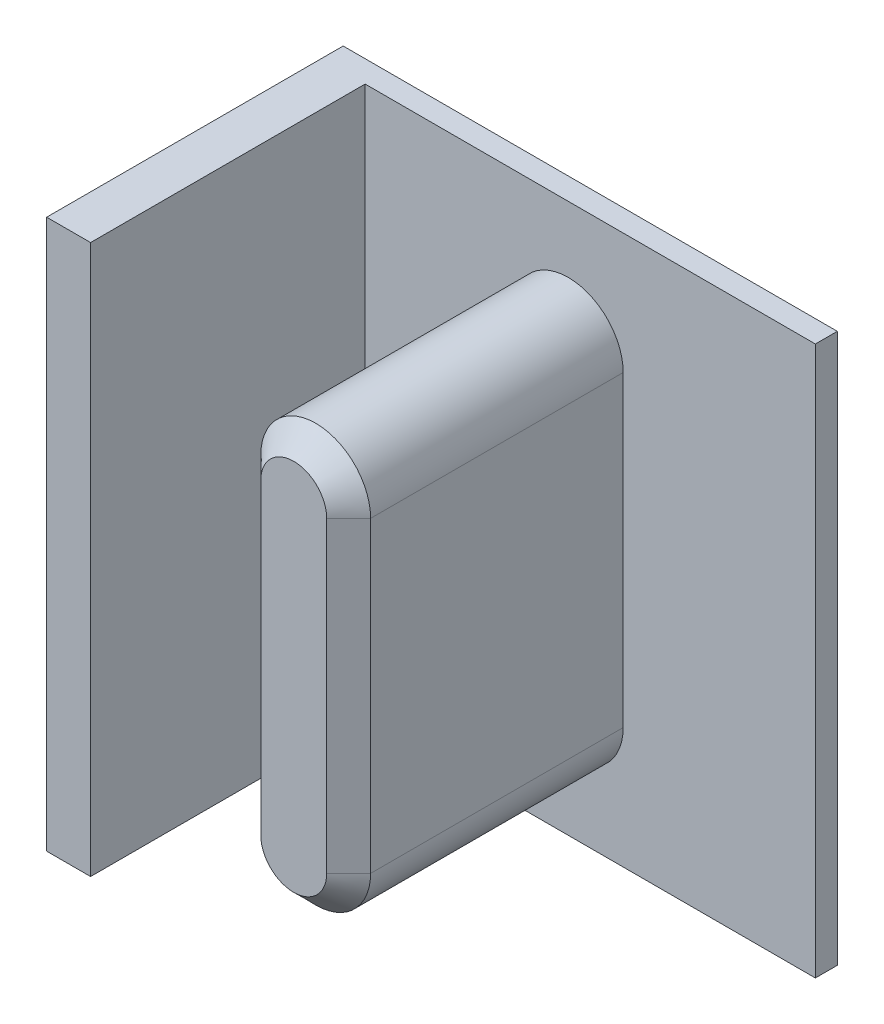
SolidWorks part; units mm, degrees
ref_plane "Front Plane" through (0, 0, 0) normal (0, 0, 1) x (1, 0, 0)
ref_plane "Top Plane" through (0, 0, 0) normal (0, 1, 0) x (1, 0, 0)
ref_plane "Right Plane" through (0, 0, 0) normal (1, 0, 0) x (0, 0, -1)
sketch "Sketch1" plane through (0, 0, 0) normal (0, 0, 1) x (1, 0, 0)
  line L1 (0, 0) -> (9, 0)
  line L2 (0, 0) -> (0, 10)
  line L3 (0, 10) -> (9, 10)
  line L4 (9, 0) -> (9, 10)
  dimension "D1" = 9
  dimension "D2" = 10
extrude "Boss-Extrude1" add sketch "Sketch1" along normal blind 0.4
sketch "Sketch3" plane through (0, 0, 0.4) normal (0, 0, 1) x (1, 0, 0)
  line L0 (4.5, 2.2) -> (4.5, 7.8) construction
  line L1 (3.5, 2.2) -> (3.5, 7.8)
  line L2 (5.5, 2.2) -> (5.5, 7.8)
  line L3 (9, 0) -> (9, 10) construction
  line L5 (0, 0) -> (9, 0) construction
  arc A0 (3.5, 2.2) -> (5.5, 2.2) centre (4.5, 2.2) ccw
  arc A1 (5.5, 7.8) -> (3.5, 7.8) centre (4.5, 7.8) ccw
  point P2 (4.5, 5)
  dimension "D2" = 1
  dimension "D1" = 4.5
  dimension "D3" = 5.6
  dimension "D4" = 5
extrude "Boss-Extrude2" add sketch "Sketch3" along normal blind 5
sketch "Sketch4" plane through (0, 0, 0.4) normal (0, 0, 1) x (1, 0, 0)
  line L0 (0, 0) -> (9, 0) construction
  line L1 (0, 10) -> (0.8, 10)
  line L2 (0, 10) -> (0, 0)
  line L3 (0, 0) -> (0.8, 0)
  line L4 (0.8, 10) -> (0.8, 0)
  dimension "D1" = 0.8
extrude "Boss-Extrude3" add sketch "Sketch4" along normal blind 5
chamfer "Chamfer1" distance 0.4 angle 45 4 edges at (3.5, 5, 5.4) (4.5, 8.8, 5.4) (5.5, 5, 5.4) (4.5, 1.2, 5.4)
